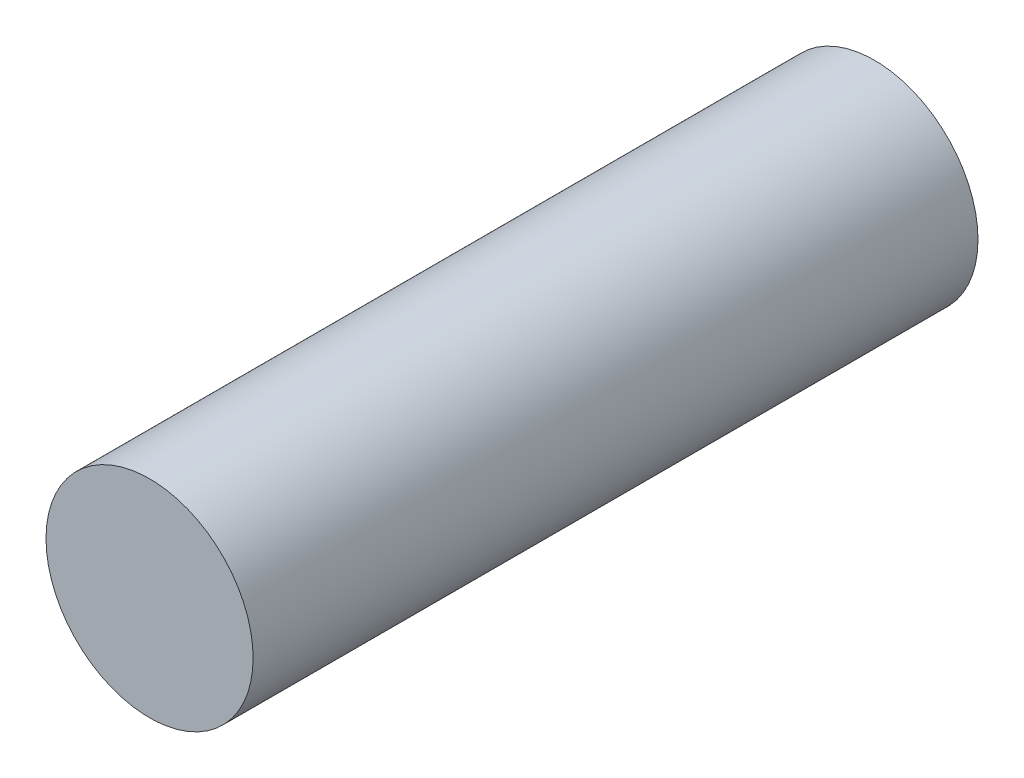
SolidWorks part; units mm, degrees
ref_plane "Front Plane" through (0, 0, 0) normal (0, 0, 1) x (1, 0, 0)
ref_plane "Top Plane" through (0, 0, 0) normal (0, 1, 0) x (1, 0, 0)
ref_plane "Right Plane" through (0, 0, 0) normal (1, 0, 0) x (0, 0, -1)
sketch "Sketch2" plane through (0, 0, 0) normal (0, 0, 1) x (1, 0, 0)
  circle A0 centre (0, 0) radius 1.25
  dimension "D1" = 2.5
sketch "Sketch3" plane through (0, 0, 0) normal (0, 0, 1) x (1, 0, 0)
  line L5 (-2, 2) -> (2, 2) construction
  line L6 (-2, 2) -> (-2, -2) construction
  line L7 (-2, -2) -> (2, -2) construction
  line L8 (2, 2) -> (2, -2) construction
  circle A0 centre (0, 0) radius 2
  point P4 (0, 2)
  point P6 (-2, 0)
  dimension "D1" = 4
extrude "Boss-Extrude1" add sketch "Sketch3" along normal blind 14
equation "\"length\"=14"
equation "\"D1@Boss-Extrude1\"=\"length\""
